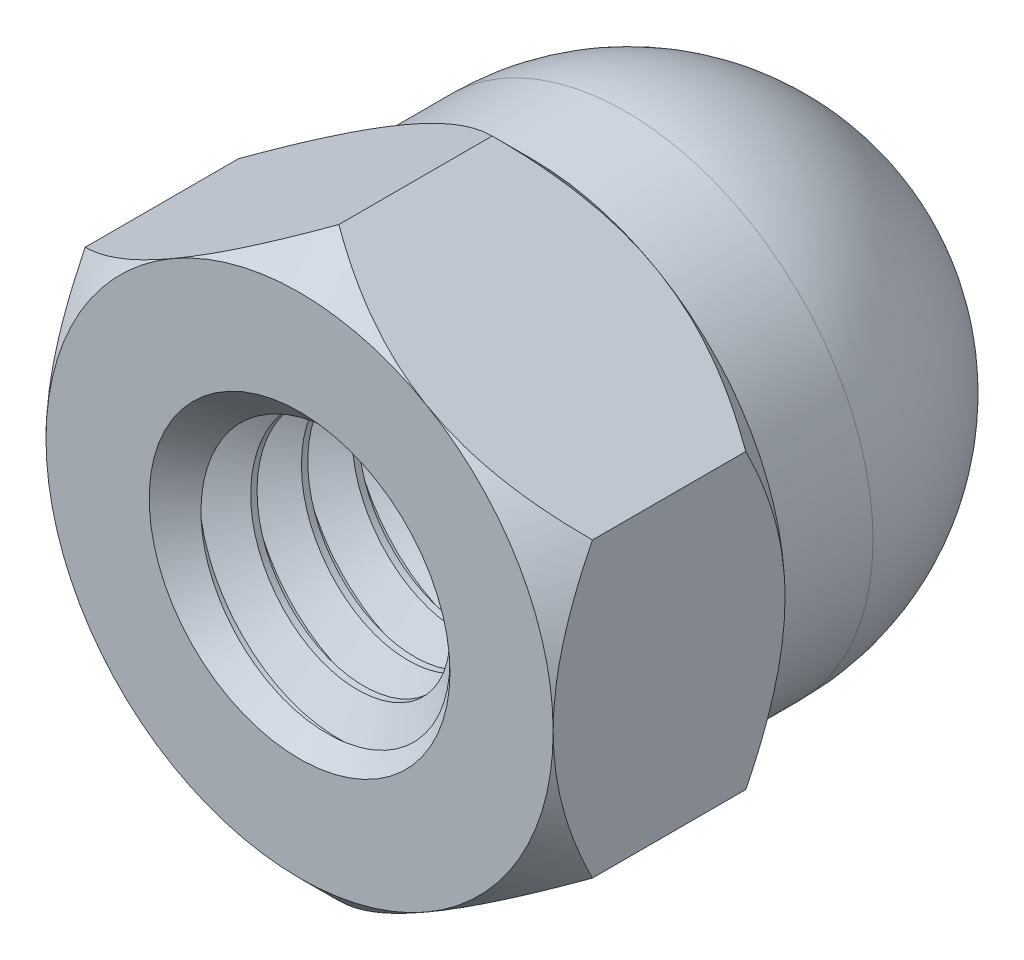
SolidWorks part; units mm, degrees
ref_plane "Front Plane" through (0, 0, 0) normal (0, 0, 1) x (1, 0, 0)
ref_plane "Top Plane" through (0, 0, 0) normal (0, 1, 0) x (1, 0, 0)
ref_plane "Right Plane" through (0, 0, 0) normal (1, 0, 0) x (0, 0, -1)
sketch "Sketch1" plane through (0, 0, 0) normal (-1, 0, 0) x (0, 0, 1)
  line L0 (-4, 0) -> (4, 0) construction
  line L1 (-4, 0) -> (-4, 3.5) construction
  line L2 (4, 3.5) -> (-4, 3.5) construction
  line L3 (4, 2) -> (-1.74, 2) construction
  line L4 (4, 0) -> (4, 3.5) construction
  line L5 (-1.74, 2) -> (-1.74, 0) construction
  line L7 (-1.74, 2) -> (-2.2759, 0) construction
  line L8 (4.6563, 2.0758) -> (4.3063, 1.4696) construction
  line L9 (4.3063, 1.4696) -> (3.9563, 2.0758) construction
  line L10 (3.9563, 2.0758) -> (4.6563, 2.0758) construction
  line L11 (4.3063, 1.4696) -> (4.3063, 1.5453) construction
  line L12 (4.3063, 2.0758) -> (4.3063, 2) construction
  line L13 (4.6125, 2) -> (4, 2) construction
  line L14 (4.2625, 1.5453) -> (4.35, 1.5453) construction
  line L15 (4.3063, 2.0379) -> (3.9781, 2.0379) construction
  line L16 (4.3063, 2.0379) -> (4.6344, 2.0379) construction
  arc A2 (-4, 0) -> (-0.5, 3.5) centre (-0.5, 0) cw construction
  point P3 (0, 0)
  point P23 (0.8, 3.5)
  dimension "Height" = 8
  dimension "Width" = 7
  dimension "Thread Depth" = 5.74
  dimension "Thread OD" = 4
  dimension "Thread Tip Angle" = 75
  dimension "Thread Pitch" = 0.7
  dimension "D1" = 0.0875
  dimension "Hex Thickness (m)" = 3.2
ref_plane "Plane1" through (0, 0, 4) normal (0, 0, 1) x (1, 0, 0)
ref_plane "Plane2" through (0, 0, 0.8) normal (0, 0, 1) x (1, 0, 0)
ref_plane "Plane3" through (0, 0, -1.74) normal (0, 0, 1) x (1, 0, 0)
sketch "Sketch7" plane through (0, 0, 4) normal (0, 0, 1) x (1, 0, 0)
  line L1 (0, 4.0415) -> (-3.5, 2.0207)
  line L2 (-3.5, 2.0207) -> (-3.5, -2.0207)
  line L3 (-3.5, -2.0207) -> (0, -4.0415)
  line L4 (0, -4.0415) -> (3.5, -2.0207)
  line L5 (3.5, -2.0207) -> (3.5, 2.0207)
  line L6 (3.5, 2.0207) -> (0, 4.0415)
  circle A0 centre (0, 0) radius 3.5 construction
  point P0 (0, 3.5)
extrude "Boss-Extrude2" add sketch "Sketch7" against normal up to vertex (3.2 mm away) up to point (0, 3.5, 0.8)
sketch "Sketch8" plane through (0, 0, 4) normal (0, 0, 1) x (1, 0, 0)
  circle A0 centre (0, 0) radius 3.5
extrude "Cut-Extrude3" cut sketch "Sketch8" against normal through all draft 45 flip side to cut
sketch "Sketch9" plane through (0, 0, 0.8) normal (0, 0, 1) x (1, 0, 0)
  circle A1 centre (0, 0) radius 3.5
  circle A2 centre (0, 0) radius 3.5
  dimension "D1" = 0
extrude "Cut-Extrude4" cut sketch "Sketch9" along normal through all draft 45 flip side to cut
sketch "Sketch10" plane through (0, 0, 0) normal (1, 0, 0) x (0, 0, -1)
  line L0 (0.5, 3.5) -> (-0.8, 3.5)
  line L1 (4, 0) -> (-4, 0) construction
  line L3 (4, 0) -> (-0.8, 0)
  line L4 (-0.8, 3.5) -> (-0.8, 0)
  arc A0 (4, 0) -> (0.5, 3.5) centre (0.5, 0) ccw construction
  arc A4 (4, 0) -> (0.5, 3.5) centre (0.5, 0) ccw
revolve "Revolve1" add sketch "Sketch10" angle 360 about L0
sketch "Sketch16" plane through (0, 0, 0) normal (0, 0, 1) x (1, 0, 0)
  line L0 (0, 0) -> (0, -2) construction
  line L1 (0, 0) -> (0.7654, -1.8478) construction
  circle A0 centre (0, 0) radius 2 construction
  point P3 (0.7654, -1.8478)
  dimension "D1" = 22.5
sketch "Sketch17" plane through (0, 0, 0) normal (1, 0, 0) x (0, 0, -1)
  line L0 (1.74, 2) -> (2.2759, 0) construction
  line L1 (-4, 2) -> (1.74, 2) construction
  line L2 (1.74, 2) -> (2.2759, 0)
  line L3 (-4, 2) -> (1.74, 2)
  line L4 (2.2759, 0) -> (1.74, -2)
  line L5 (1.74, -2) -> (-4, -2)
sketch "Sketch11" plane through (0, 0, 0) normal (1, 0, 0) x (0, 0, -1)
  line L2 (-4, 0) -> (-4, 3.5) construction
  line L3 (-4, 2) -> (1.74, 2) construction
  line L6 (-4, 0) -> (-4, 2)
  line L7 (-4, 2) -> (1.74, 2)
  line L8 (1.74, 2) -> (2.2759, 0) construction
  line L9 (1.74, 2) -> (2.2759, 0)
  line L10 (4, 0) -> (-4, 0) construction
  line L11 (2.2759, 0) -> (-4, 0)
revolve "Cut-Revolve1" cut sketch "Sketch11" angle 360 about L0
sketch "Sketch12" plane through (0, 0, 4) normal (0, 0, 1) x (1, 0, 0)
  circle A0 centre (0, 0) radius 2
  point P0 (0, 2)
curve "Helix/Spiral1" pitch 0.7 height 6.44 turns 9.2
sketch "Sketch13" plane through (0, 0, 0) normal (1, 0, 0) x (0, 0, -1)
  line L0 (-4.6344, 2.0379) -> (-4.35, 1.5453)
  line L1 (-4.35, 1.5453) -> (-4.2625, 1.5453)
  line L2 (-4.2625, 1.5453) -> (-3.9781, 2.0379)
  line L3 (-3.9781, 2.0379) -> (-4.6344, 2.0379)
sweep "Sweep1" add profiles "Sketch13" path "Helix/Spiral1"
sketch "Sketch14" plane through (0, 0, 0) normal (1, 0, 0) x (0, 0, -1)
  line L0 (4, 0) -> (4, 3.5) construction
  line L1 (0.5, 3.414) -> (-0.8, 3.414)
  line L2 (4, 1) -> (4, 3.5) construction
  line L4 (4, 1) -> (3.828, 1) construction
  line L5 (1.74, 2) -> (1.74, 0) construction
  line L7 (4.172, 3.5) -> (4.172, 1)
  line L8 (4.172, 1) -> (4, 1) construction
  line L10 (4.172, 1) -> (4.172, 0)
  line L12 (4.172, 0) -> (4, 0)
  line L13 (4, 0) -> (-4, 0) construction
  line L14 (4, 3.5) -> (0.5, 3.5)
  line L15 (4, 3.5) -> (4.172, 3.5)
  line L17 (0.5, 3.5) -> (0.5, 3.328) construction
  line L21 (4, 0) -> (4, -2.8136) construction
  line L22 (-4, 3.5) -> (4, 3.5) construction
  line L23 (-0.8, 3.5) -> (-0.8, 3.0311) construction
  line L24 (0.5, 3.5) -> (-0.8, 3.5)
  line L25 (-0.8, 3.5) -> (-0.8, 3.414)
  line L26 (0.5, 3.5) -> (0.5, -3.5) construction
  arc A0 (4, 0) -> (0.5, 3.414) centre (0.5, -0.0871) ccw
  point P9 (1.74, 1)
revolve "Cut-Revolve4" cut sketch "Sketch14" angle 360 about L0
sketch "Sketch15" plane through (0, 0, 4) normal (0, 0, 1) x (1, 0, 0)
  circle A0 centre (0, 0) radius 2.0758
extrude "Cut-Extrude5" cut sketch "Sketch15" against normal through all draft 45 and the other way through all draft 45
equation "\"D1@Sketch1\" = \"Thread Pitch@Sketch1\" / 8"
equation "\"D3@Helix/Spiral1\" = \"Thread Depth@Sketch1\" + \"Thread Pitch@Sketch1\""
equation "\"D4@Helix/Spiral1\" = \"Thread Pitch@Sketch1\""
